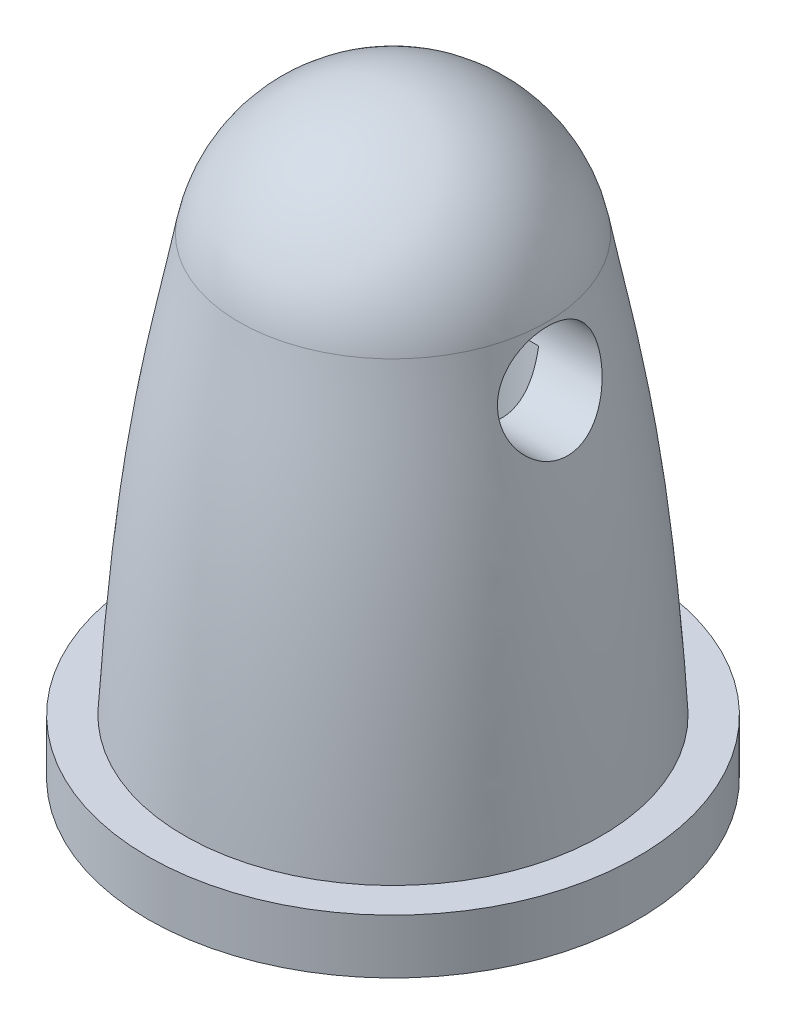
SolidWorks part; units mm, degrees
ref_plane "Front Plane" through (0, 0, 0) normal (0, 0, 1) x (1, 0, 0)
ref_plane "Top Plane" through (0, 0, 0) normal (0, 1, 0) x (1, 0, 0)
ref_plane "Right Plane" through (0, 0, 0) normal (1, 0, 0) x (0, 0, -1)
sketch "Sketch1" plane through (0, 0, 0) normal (0, 0, 1) x (1, 0, 0)
  line L0 (0, 0) -> (-5.75, 0)
  line L4 (0, 15) -> (0, 0)
  arc A0 (-4.2417, 11.5) -> (0, 15) centre (0, 10.6797) cw
  spline S0 degree 3 poles (-5.75, 0) (-5.3855, 6.4999) (-4.8014, 8.4982) (-4.2417, 11.5) knots 0 0 0 0 1 1 1 1
  dimension "D1" = 3.5
  dimension "D2" = 15
  dimension "D3" = 5.75
revolve "Revolve1" add sketch "Sketch1" angle 360 about L4
sketch "Sketch3" plane through (0, 0, 0) normal (0, -1, 0) x (1, 0, 0)
  circle A0 centre (0, 0) radius 6.75
  circle A2 centre (0, 0) radius 5.75 construction
  dimension "D1" = 1
extrude "Boss-Extrude1" add sketch "Sketch3" along normal blind 1.5
sketch "Sketch5" plane through (0, -1.5, 0) normal (0, -1, 0) x (1, 0, 0)
  circle A0 centre (0, 0) radius 3
  dimension "D1" = 6
extrude "Cut-Extrude1" cut sketch "Sketch5" against normal blind 11
sketch "Sketch6" plane through (0, 0, 0) normal (1, 0, 0) x (0, 0, -1)
  circle A0 centre (0, 10) radius 1.4081
  dimension "D1" = 10
extrude "Cut-Extrude2" cut sketch "Sketch6" against normal through all both and the other way through all
